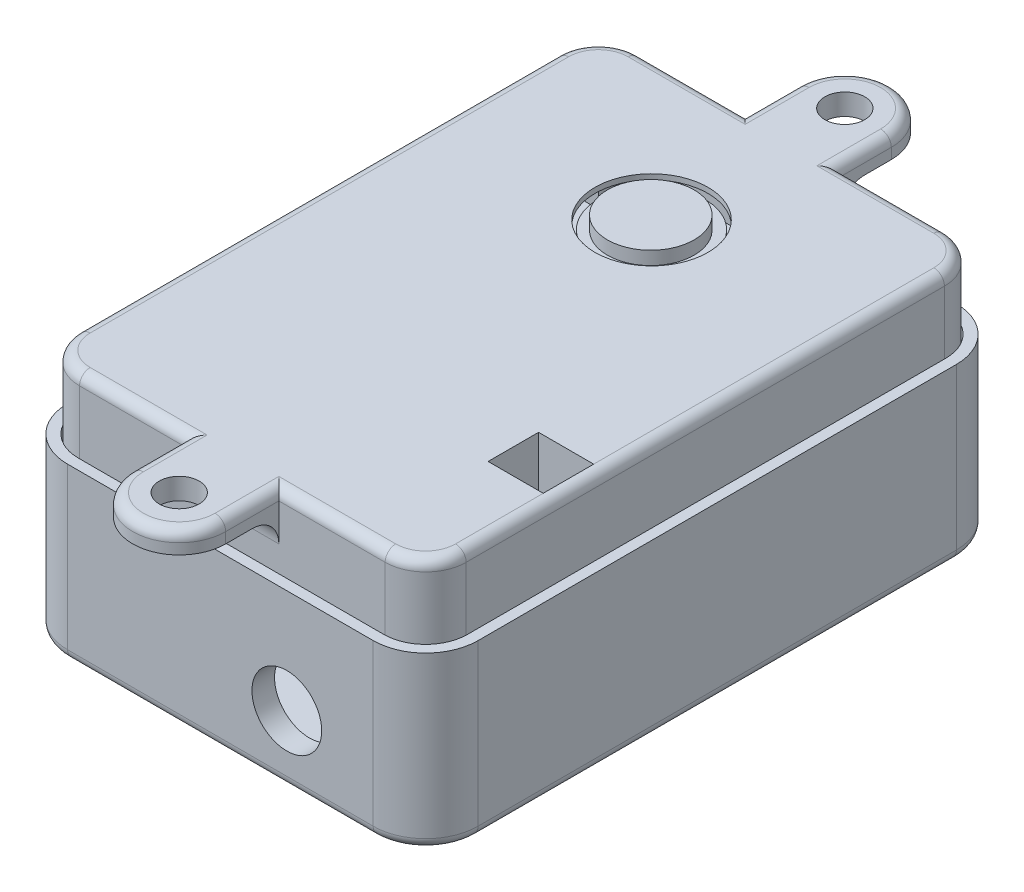
SolidWorks part; units mm, degrees
other "ESP32 Cam"
ref_plane "Front Plane" through (0, 0, 0) normal (0, 0, 1) x (1, 0, 0)
ref_plane "Top Plane" through (0, 0, 0) normal (0, 1, 0) x (1, 0, 0)
ref_plane "Right Plane" through (0, 0, 0) normal (1, 0, 0) x (0, 0, -1)
sketch "Sketch1" plane through (0, 0, 0) normal (0, 1, 0) x (1, 0, 0)
  line L1 (-11.5, 20) -> (11.5, 20)
  line L2 (-13.5, 18) -> (-13.5, -18)
  line L3 (-11.5, -20) -> (11.5, -20)
  line L4 (13.5, 18) -> (13.5, -18)
  line L5 (-13.5, 20) -> (13.5, -20) construction
  line L6 (-13.5, -20) -> (13.5, 20) construction
  arc A0 (-11.5, 20) -> (-13.5, 18) centre (-11.5, 18) ccw
  arc A1 (11.5, 20) -> (13.5, 18) centre (11.5, 18) cw
  arc A2 (11.5, -20) -> (13.5, -18) centre (11.5, -18) ccw
  arc A3 (-13.5, -18) -> (-11.5, -20) centre (-11.5, -18) ccw
  point P0 (0, 0)
  dimension "D3" = 2
  dimension "D1" = 27
  dimension "D2" = 40
extrude "Boss-Extrude1" add sketch "Sketch1" along normal blind 1
sketch "Sketch2" plane through (0, 1, 0) normal (0, 1, 0) x (1, 0, 0)
  line L0 (0, 0) -> (0, 20) construction
  line L1 (11.5, 20) -> (-11.5, 20) construction
  line L3 (-7.5, 20) -> (7.5, 20)
  line L4 (-7.5, 20) -> (-7.5, 5)
  line L5 (-7.5, 5) -> (7.5, 5)
  line L6 (7.5, 20) -> (7.5, 5)
  line L7 (-7.5, 20) -> (7.5, 5) construction
  line L8 (-7.5, 5) -> (7.5, 20) construction
  point P5 (0, 12.5)
  dimension "D1" = 15
extrude "Boss-Extrude2" add sketch "Sketch2" along normal blind 2
sketch "Sketch3" plane through (0, 3, 0) normal (0, 1, 0) x (1, 0, 0)
  line L0 (0, 5) -> (0, 20) construction
  line L1 (-7.5, 5) -> (7.5, 5) construction
  line L2 (7.5, 20) -> (-7.5, 20) construction
  circle A0 centre (0, 10.5) radius 4
  dimension "D1" = 8
  dimension "D2" = 5.5
extrude "Boss-Extrude3" add sketch "Sketch3" along normal blind 6.25
sketch "Sketch5" plane through (0, 1, 0) normal (0, 1, 0) x (1, 0, 0)
  line L0 (-11.5, -20) -> (11.5, -20) construction
  line L1 (10, -8) -> (13, -8)
  line L2 (10, -8) -> (10, -11)
  line L3 (10, -11) -> (13, -11)
  line L4 (13, -8) -> (13, -11)
  line L5 (10, -8) -> (13, -11) construction
  line L6 (10, -11) -> (13, -8) construction
  line L7 (13.5, -18) -> (13.5, 18) construction
  point P0 (11.5, -9.5)
  dimension "D1" = 3
  dimension "D2" = 10.5
  dimension "D3" = 2
extrude "Boss-Extrude4" add sketch "Sketch5" along normal blind 1
sketch "Sketch6" plane through (0, 9.25, 0) normal (0, 1, 0) x (1, 0, 0)
  line L37 (7.5, 21.05) -> (-7.5, 21.05)
  line L38 (-7.5, 21.05) -> (-11.5, 21.05)
  line L39 (-14.55, 18) -> (-14.55, -18)
  line L40 (-11.5, -21.05) -> (11.5, -21.05)
  line L41 (14.55, -18) -> (14.55, 18)
  line L42 (11.5, 21.05) -> (7.5, 21.05)
  line L43 (7.5, 20.25) -> (-7.5, 20.25)
  line L44 (11.5, 20.25) -> (7.5, 20.25)
  line L45 (13.75, -18) -> (13.75, 18)
  line L46 (-11.5, -20.25) -> (11.5, -20.25)
  line L47 (-13.75, 18) -> (-13.75, -18)
  line L48 (-7.5, 20.25) -> (-11.5, 20.25)
  line L55 (7.5, 20.25) -> (-7.5, 20.25) construction
  line L56 (11.5, 20.25) -> (7.5, 20.25) construction
  line L57 (13.75, -18) -> (13.75, 18) construction
  line L58 (-11.5, -20.25) -> (11.5, -20.25) construction
  line L59 (-13.75, 18) -> (-13.75, -18) construction
  line L60 (-7.5, 20.25) -> (-11.5, 20.25) construction
  circle A6 centre (0, 10.5) radius 4.25
  circle A8 centre (0, 10.5) radius 4.25
  arc A36 (-11.5, 21.05) -> (-14.55, 18) centre (-11.5, 18) ccw
  arc A37 (-14.55, -18) -> (-11.5, -21.05) centre (-11.5, -18) ccw
  arc A38 (11.5, -21.05) -> (14.55, -18) centre (11.5, -18) ccw
  arc A39 (14.55, 18) -> (11.5, 21.05) centre (11.5, 18) ccw
  arc A40 (13.75, 18) -> (11.5, 20.25) centre (11.5, 18) ccw
  arc A41 (11.5, -20.25) -> (13.75, -18) centre (11.5, -18) ccw
  arc A42 (-13.75, -18) -> (-11.5, -20.25) centre (-11.5, -18) ccw
  arc A43 (-11.5, 20.25) -> (-13.75, 18) centre (-11.5, 18) ccw
  arc A44 (13.75, 18) -> (11.5, 20.25) centre (11.5, 18) ccw construction
  arc A45 (11.5, -20.25) -> (13.75, -18) centre (11.5, -18) ccw construction
  arc A46 (-13.75, -18) -> (-11.5, -20.25) centre (-11.5, -18) ccw construction
  arc A47 (-11.5, 20.25) -> (-13.75, 18) centre (-11.5, 18) ccw construction
  dimension "D1" = 0.25
  dimension "D2" = 0.8
  dimension "D3" = 0.25
extrude "Boss-Extrude5" add sketch "Sketch6" along normal blind 0.4 from offset 0.25 separate body
sketch "Sketch8" plane through (0, 9.5, 0) normal (0, -1, 0) x (1, 0, 0)
  line L4 (-11.5, -21.05) -> (11.5, -21.05)
  line L5 (14.55, -18) -> (14.55, 18)
  line L6 (11.5, 21.05) -> (-11.5, 21.05)
  line L7 (-14.55, 18) -> (-14.55, -18)
  line L8 (-11.5, -21.05) -> (11.5, -21.05)
  line L9 (14.55, -18) -> (14.55, 18)
  line L10 (11.5, 21.05) -> (-11.5, 21.05)
  line L11 (-14.55, 18) -> (-14.55, -18)
  line L16 (-11.5, -20.25) -> (11.5, -20.25)
  line L17 (13.75, -18) -> (13.75, 18)
  line L18 (11.5, 20.25) -> (-11.5, 20.25)
  line L19 (-13.75, 18) -> (-13.75, -18)
  line L20 (-11.5, -20.25) -> (11.5, -20.25)
  line L21 (13.75, -18) -> (13.75, 18)
  line L22 (11.5, 20.25) -> (-11.5, 20.25)
  line L23 (-13.75, 18) -> (-13.75, -18)
  arc A4 (11.5, -21.05) -> (14.55, -18) centre (11.5, -18) ccw
  arc A5 (14.55, 18) -> (11.5, 21.05) centre (11.5, 18) ccw
  arc A6 (-11.5, 21.05) -> (-14.55, 18) centre (-11.5, 18) ccw
  arc A7 (-14.55, -18) -> (-11.5, -21.05) centre (-11.5, -18) ccw
  arc A8 (11.5, -21.05) -> (14.55, -18) centre (11.5, -18) ccw
  arc A9 (14.55, 18) -> (11.5, 21.05) centre (11.5, 18) ccw
  arc A10 (-11.5, 21.05) -> (-14.55, 18) centre (-11.5, 18) ccw
  arc A11 (-14.55, -18) -> (-11.5, -21.05) centre (-11.5, -18) ccw
  arc A16 (11.5, -20.25) -> (13.75, -18) centre (11.5, -18) ccw
  arc A17 (13.75, 18) -> (11.5, 20.25) centre (11.5, 18) ccw
  arc A18 (-11.5, 20.25) -> (-13.75, 18) centre (-11.5, 18) ccw
  arc A19 (-13.75, -18) -> (-11.5, -20.25) centre (-11.5, -18) ccw
  arc A20 (11.5, -20.25) -> (13.75, -18) centre (11.5, -18) ccw
  arc A21 (13.75, 18) -> (11.5, 20.25) centre (11.5, 18) ccw
  arc A22 (-11.5, 20.25) -> (-13.75, 18) centre (-11.5, 18) ccw
  arc A23 (-13.75, -18) -> (-11.5, -20.25) centre (-11.5, -18) ccw
  dimension "D1" = 0
  dimension "D2" = 0.8
extrude "Boss-Extrude7" add sketch "Sketch8" along normal up to vertex (9.5 mm away) up to point (-11.5, 0, 20)
sketch "Sketch9" plane through (0, 9.5, 0) normal (0, -1, 0) x (1, 0, 0)
  line L0 (13.75, 18) -> (11.5, 18)
  line L1 (11.5, 18) -> (11.5, 20.25)
  line L2 (6.0225, 0) -> (-6.0225, 0) construction
  line L3 (11.5, -18) -> (11.5, -20.25)
  line L4 (13.75, -18) -> (11.5, -18)
  line L5 (0, -6.0225) -> (0, 6.0225) construction
  line L6 (-13.75, -18) -> (-11.5, -18)
  line L7 (-11.5, -18) -> (-11.5, -20.25)
  line L8 (-11.5, 18) -> (-11.5, 20.25)
  line L9 (-13.75, 18) -> (-11.5, 18)
  arc A0 (13.75, 18) -> (11.5, 20.25) centre (11.5, 18) ccw construction
  arc A1 (13.75, 18) -> (11.5, 20.25) centre (11.5, 18) ccw
  arc A2 (13.75, -18) -> (11.5, -20.25) centre (11.5, -18) cw
  arc A3 (-13.75, -18) -> (-11.5, -20.25) centre (-11.5, -18) ccw
  arc A4 (-13.75, 18) -> (-11.5, 20.25) centre (-11.5, 18) cw
extrude "Boss-Extrude9" add sketch "Sketch9" along normal offset from surface (8.4 mm away) 0.1 up to face at (0, 1, -4.1667)
sketch "Sketch11" plane through (0, 9.9, 0) normal (0, 1, 0) x (1, 0, 0)
  line L1 (13.75, -7.6) -> (9.6, -7.6)
  line L2 (9.6, -7.6) -> (9.6, -11.4)
  line L3 (9.6, -11.4) -> (13.75, -11.4)
  line L4 (13, -11) -> (13, -8)
  line L5 (13, -8) -> (10, -8)
  line L6 (10, -8) -> (10, -11)
  line L7 (10, -11) -> (13, -11)
  line L8 (13, -11) -> (13, -8) construction
  line L9 (13, -8) -> (10, -8) construction
  line L10 (10, -8) -> (10, -11) construction
  line L11 (10, -11) -> (13, -11) construction
  line L12 (13.75, 18) -> (13.75, -18) construction
  line L13 (13.75, -7.6) -> (13.75, -11.4)
  line L14 (9.6, -11.4) -> (13.4, -11.4) construction
  line L15 (13.4, -11.4) -> (13.4, -7.6) construction
  line L16 (13.4, -7.6) -> (9.6, -7.6) construction
  dimension "D1" = 0
  dimension "D2" = 0.4
extrude "Cut-Extrude1" cut sketch "Sketch11" against normal up to vertex (0.4 mm away) up to point (11.5, 9.5, 18)
sketch "Sketch12" plane through (0, 0, 0) normal (0, -1, 0) x (1, 0, 0)
  line L0 (0, 0) -> (0, 20) construction
  line L1 (-11.5, 20) -> (11.5, 20) construction
  line L3 (9.375, -5.65) -> (-9.375, -5.65)
  line L4 (9.375, -5.65) -> (9.375, 20)
  line L5 (9.375, 20) -> (-9.375, 20)
  line L6 (-9.375, -5.65) -> (-9.375, 20)
  line L7 (9.375, -5.65) -> (-9.375, 20) construction
  line L8 (9.375, 20) -> (-9.375, -5.65) construction
  point P5 (0, 7.175)
  dimension "D1" = 18.75
  dimension "D2" = 25.65
extrude "Boss-Extrude10" add sketch "Sketch12" along normal blind 0.75
sketch "Sketch13" plane through (0, -0.75, 0) normal (0, -1, 0) x (1, 0, 0)
  line L0 (0, -5.65) -> (0, 20) construction
  line L1 (-9.375, -5.65) -> (9.375, -5.65) construction
  line L2 (8, 12.35) -> (2, 12.35) construction
  line L3 (2, 12.35) -> (-8, 12.35)
  line L4 (8, 9.35) -> (8, -5.15)
  line L5 (8, -5.15) -> (-8, -5.15)
  line L6 (-8, 12.35) -> (-8, -5.15)
  line L7 (8, 12.35) -> (-8, -5.15) construction
  line L8 (8, -5.15) -> (-8, 12.35) construction
  line L11 (8, 9.35) -> (2, 9.35)
  line L12 (2, 12.35) -> (2, 9.35)
  line L13 (8, 12.35) -> (8, 9.35) construction
  line L14 (9.375, 20) -> (11.5, 20) construction
  point P5 (0, 3.6)
  dimension "D1" = 16
  dimension "D2" = 17.5
  dimension "D3" = 3
  dimension "D4" = 6
  dimension "D5" = 0.5
extrude "Boss-Extrude11" add sketch "Sketch13" along normal blind 2.3
sketch "Sketch14" plane through (0, 0, 0) normal (0, -1, 0) x (1, 0, 0)
  line L0 (9.375, 20) -> (11.5, 20) construction
  line L1 (12.75, -16.2) -> (10.25, -16.2)
  line L2 (12.75, -16.2) -> (12.75, 4)
  line L3 (12.75, 4) -> (10.25, 4)
  line L4 (10.25, -16.2) -> (10.25, 4)
  line L5 (12.75, -16.2) -> (10.25, 4) construction
  line L6 (12.75, 4) -> (10.25, -16.2) construction
  line L7 (13.5, 18) -> (13.5, -18) construction
  point P0 (11.5, -6.1)
  dimension "D1" = 20.2
  dimension "D2" = 2.5
  dimension "D3" = 16
  dimension "D4" = 0.75
extrude "Boss-Extrude12" add sketch "Sketch14" along normal blind 2.45
sketch "Sketch16" plane through (0, -2.45, 0) normal (0, -1, 0) x (1, 0, 0)
  line L0 (11.5, 4) -> (11.5, -16.2) construction
  line L3 (11.2, 3) -> (11.8, 3)
  line L8 (11.2, 3) -> (11.2, 2.4)
  line L9 (11.2, 2.4) -> (11.8, 2.4)
  line L10 (11.8, 3) -> (11.8, 2.4)
  line L11 (12.75, 4) -> (10.25, 4) construction
  line L12 (10.25, -16.2) -> (12.75, -16.2) construction
  dimension "D1" = 0.6
  dimension "D2" = 1
extrude "Boss-Extrude14" add sketch "Sketch16" along normal blind 5.5
pattern_linear "LPattern1" count 8 spacing 2.5 along (0, 0, -1) of "Boss-Extrude14"
sketch "Sketch17" plane through (0, -3.05, 0) normal (0, -1, 0) x (1, 0, 0)
  line L14 (-11.5, -21.95) -> (11.5, -21.95)
  line L15 (15.45, -18) -> (15.45, 18)
  line L16 (-11.5, -21.15) -> (11.5, -21.15)
  line L17 (-14.65, 18) -> (-14.65, -18)
  line L18 (11.5, 21.15) -> (-11.5, 21.15)
  line L19 (-11.5, -21.15) -> (11.5, -21.15)
  line L20 (-14.65, 18) -> (-14.65, -18)
  line L21 (11.5, 21.15) -> (-11.5, 21.15)
  line L22 (14.65, -18) -> (14.65, 18)
  line L23 (11.5, 21.95) -> (-11.5, 21.95)
  line L24 (-15.45, 18) -> (-15.45, -18)
  arc A16 (11.5, -21.95) -> (15.45, -18) centre (11.5, -18) ccw
  arc A17 (15.45, 18) -> (11.5, 21.95) centre (11.5, 18) ccw
  arc A18 (-11.5, 21.95) -> (-15.45, 18) centre (-11.5, 18) ccw
  arc A19 (-15.45, -18) -> (-11.5, -21.95) centre (-11.5, -18) ccw
  arc A20 (11.5, -21.15) -> (14.65, -18) centre (11.5, -18) ccw
  arc A21 (-14.65, -18) -> (-11.5, -21.15) centre (-11.5, -18) ccw
  arc A22 (-11.5, 21.15) -> (-14.65, 18) centre (-11.5, 18) ccw
  arc A23 (14.65, 18) -> (11.5, 21.15) centre (11.5, 18) ccw
  arc A24 (11.5, -21.15) -> (14.65, -18) centre (11.5, -18) ccw
  arc A25 (-14.65, -18) -> (-11.5, -21.15) centre (-11.5, -18) ccw
  arc A26 (-11.5, 21.15) -> (-14.65, 18) centre (-11.5, 18) ccw
  arc A27 (14.65, 18) -> (11.5, 21.15) centre (11.5, 18) ccw
  dimension "D1" = 0.1
  dimension "D2" = 0.8
extrude "Boss-Extrude15" add sketch "Sketch17" against normal blind 12.5 from offset 5 separate body
sketch "Sketch18" plane through (0, -8.05, 0) normal (0, -1, 0) x (1, 0, 0)
  line L0 (-11.5, -20.25) -> (11.5, -20.25) construction
  line L1 (-13.75, 18) -> (-13.75, -18) construction
  line L2 (13.75, -18) -> (13.75, 18) construction
  line L3 (11.5, 20.25) -> (-11.5, 20.25) construction
  line L4 (-11.5, -20.25) -> (11.5, -20.25)
  line L5 (-13.75, 18) -> (-13.75, -18)
  line L6 (13.75, -18) -> (13.75, 18)
  line L7 (11.5, 20.25) -> (-11.5, 20.25)
  line L8 (-11.5, -21.15) -> (11.5, -21.15) construction
  line L9 (-14.65, 18) -> (-14.65, -18) construction
  line L10 (11.5, 21.15) -> (-11.5, 21.15) construction
  line L11 (14.65, -18) -> (14.65, 18) construction
  line L12 (-11.5, -21.15) -> (11.5, -21.15)
  line L13 (-14.65, 18) -> (-14.65, -18)
  line L14 (11.5, 21.15) -> (-11.5, 21.15)
  line L15 (14.65, -18) -> (14.65, 18)
  arc A0 (11.5, -20.25) -> (13.75, -18) centre (11.5, -18) ccw construction
  arc A1 (-13.75, -18) -> (-11.5, -20.25) centre (-11.5, -18) ccw construction
  arc A2 (-11.5, 20.25) -> (-13.75, 18) centre (-11.5, 18) ccw construction
  arc A3 (13.75, 18) -> (11.5, 20.25) centre (11.5, 18) ccw construction
  arc A4 (11.5, -20.25) -> (13.75, -18) centre (11.5, -18) ccw
  arc A5 (-13.75, -18) -> (-11.5, -20.25) centre (-11.5, -18) ccw
  arc A6 (-11.5, 20.25) -> (-13.75, 18) centre (-11.5, 18) ccw
  arc A7 (13.75, 18) -> (11.5, 20.25) centre (11.5, 18) ccw
  arc A8 (11.5, -21.15) -> (14.65, -18) centre (11.5, -18) ccw construction
  arc A9 (-14.65, -18) -> (-11.5, -21.15) centre (-11.5, -18) ccw construction
  arc A10 (-11.5, 21.15) -> (-14.65, 18) centre (-11.5, 18) ccw construction
  arc A11 (14.65, 18) -> (11.5, 21.15) centre (11.5, 18) ccw construction
  arc A12 (11.5, -21.15) -> (14.65, -18) centre (11.5, -18) ccw
  arc A13 (-14.65, -18) -> (-11.5, -21.15) centre (-11.5, -18) ccw
  arc A14 (-11.5, 21.15) -> (-14.65, 18) centre (-11.5, 18) ccw
  arc A15 (14.65, 18) -> (11.5, 21.15) centre (11.5, 18) ccw
extrude "Boss-Extrude16" add sketch "Sketch18" against normal offset from surface (7.95 mm away) 0.1 up to face at (0, 0, 0)
sketch "Sketch19" plane through (0, -8.05, 0) normal (0, -1, 0) x (1, 0, 0)
  line L165 (0, -6.0225) -> (0, 6.0225) construction
  line L166 (-13.25, -16.7) -> (-13.25, 4.5)
  line L167 (-13.25, 4.5) -> (-9.75, 4.5)
  line L168 (-9.75, 4.5) -> (-9.75, -16.7)
  line L169 (13.25, 4.5) -> (9.75, 4.5)
  line L170 (13.25, -16.7) -> (13.25, 4.5)
  line L171 (9.75, -16.7) -> (13.25, -16.7)
  line L172 (9.75, 4.5) -> (9.75, -16.7)
  line L173 (13.25, 4.5) -> (9.75, 4.5)
  line L174 (13.25, -16.7) -> (13.25, 4.5)
  line L175 (9.75, -16.7) -> (13.25, -16.7)
  line L176 (9.75, 4.5) -> (9.75, -16.7)
  line L177 (-9.75, -16.7) -> (-13.25, -16.7)
  line L178 (11.5, 21.95) -> (-11.5, 21.95) construction
  line L179 (-15.45, 18) -> (-15.45, -18) construction
  line L180 (-11.5, -21.95) -> (11.5, -21.95) construction
  line L181 (15.45, -18) -> (15.45, 18) construction
  line L182 (11.5, 21.95) -> (-11.5, 21.95)
  line L183 (-15.45, 18) -> (-15.45, -18)
  line L184 (-11.5, -21.95) -> (11.5, -21.95)
  line L185 (15.45, -18) -> (15.45, 18)
  arc A0 (15.45, 18) -> (11.5, 21.95) centre (11.5, 18) ccw construction
  arc A1 (-11.5, 21.95) -> (-15.45, 18) centre (-11.5, 18) ccw construction
  arc A2 (-15.45, -18) -> (-11.5, -21.95) centre (-11.5, -18) ccw construction
  arc A3 (11.5, -21.95) -> (15.45, -18) centre (11.5, -18) ccw construction
  arc A4 (15.45, 18) -> (11.5, 21.95) centre (11.5, 18) ccw
  arc A5 (-11.5, 21.95) -> (-15.45, 18) centre (-11.5, 18) ccw
  arc A6 (-15.45, -18) -> (-11.5, -21.95) centre (-11.5, -18) ccw
  arc A7 (11.5, -21.95) -> (15.45, -18) centre (11.5, -18) ccw
  dimension "D1" = 0.5
extrude "Boss-Extrude17" add sketch "Sketch19" along normal blind 0.4
sketch "Sketch20" plane through (0, 0, 21.95) normal (0, 0, 1) x (1, 0, 0)
  line L0 (2, -3.05) -> (2, -0.75) construction
  line L1 (8, -0.75) -> (2, -0.75) construction
  line L2 (8, -3.05) -> (8, -0.75) construction
  line L3 (8, -3.05) -> (2, -3.05) construction
  line L4 (2, -3.05) -> (2, -0.75) construction
  line L5 (8, -0.75) -> (2, -0.75) construction
  line L6 (8, -3.05) -> (8, -0.75) construction
  line L7 (8, -3.05) -> (2, -3.05) construction
  line L8 (8, -3.05) -> (2, -0.75) construction
  line L9 (8, -0.75) -> (2, -3.05) construction
  line L10 (5, -1.9) -> (5, -3.375) construction
  line L12 (9.375, -0.75) -> (-9.375, -0.75) construction
  line L13 (9.375, -0.75) -> (-9.375, -0.75) construction
  circle A0 centre (5, -3.375) radius 2.625
  dimension "D1" = 5.25
extrude "Cut-Extrude2" cut sketch "Sketch20" against normal up to next (1.7 mm away) contours A0 region at (5, -3.375, 21.95)
sketch "Sketch22" plane through (0, -8.05, 0) normal (0, 1, 0) x (1, 0, 0)
  line L0 (13.75, -18) -> (11.5, -18)
  line L1 (11.5, -18) -> (11.5, -20.25)
  line L2 (-6.0225, 0) -> (6.0225, 0) construction
  line L3 (11.5, 18) -> (11.5, 20.25)
  line L4 (13.75, 18) -> (11.5, 18)
  line L5 (0, -6.0225) -> (0, 6.0225) construction
  line L6 (-13.75, 18) -> (-11.5, 18)
  line L7 (-11.5, 18) -> (-11.5, 20.25)
  line L8 (-11.5, -18) -> (-11.5, -20.25)
  line L9 (-13.75, -18) -> (-11.5, -18)
  arc A0 (11.5, -20.25) -> (13.75, -18) centre (11.5, -18) ccw construction
  arc A1 (11.5, -20.25) -> (13.75, -18) centre (11.5, -18) ccw
  arc A2 (11.5, 20.25) -> (13.75, 18) centre (11.5, 18) cw
  arc A3 (-11.5, 20.25) -> (-13.75, 18) centre (-11.5, 18) ccw
  arc A4 (-11.5, -20.25) -> (-13.75, -18) centre (-11.5, -18) cw
extrude "Boss-Extrude18" add sketch "Sketch22" along normal up to vertex (7.95 mm away) up to point (11.5, -0.1, -20.25)
sketch "Sketch23" plane through (0, 9.5, 0) normal (0, -1, 0) x (1, 0, 0)
  line L1 (9.6, 11.4) -> (13.75, 11.4) construction
  line L2 (9.6, 7.6) -> (9.6, 11.4) construction
  line L3 (13.75, 7.6) -> (9.6, 7.6) construction
  line L5 (9.6, 11.4) -> (13.75, 11.4)
  line L6 (9.6, 7.6) -> (9.6, 11.4)
  line L7 (13.75, 7.6) -> (9.6, 7.6)
  line L8 (13.75, 6.8) -> (8.8, 6.8)
  line L9 (8.8, 6.8) -> (8.8, 12.2)
  line L10 (8.8, 12.2) -> (13.75, 12.2)
  line L11 (13.75, 7.6) -> (13.75, 6.8)
  line L12 (13.75, 12.2) -> (13.75, 11.4)
  dimension "D1" = 0.8
extrude "Boss-Extrude19" add sketch "Sketch23" along normal offset from surface (7.4 mm away) 1 up to face at (12.4053, 1.1, 18.9053)
mirror "Mirror1" about plane through (0, 0, 0) normal (1, 0, 0) of "LPattern1", "Boss-Extrude12"
sketch "Sketch24" plane through (0, 9.9, 0) normal (0, 1, 0) x (1, 0, 0)
  line L0 (0, 0) -> (0, 25.05) construction
  line L2 (-3.5, 25.05) -> (-3.5, 21.05)
  line L8 (11.5, 21.05) -> (-11.5, 21.05) construction
  line L9 (3.5, 25.05) -> (3.5, 21.05)
  line L10 (-3.5, 21.05) -> (3.5, 21.05)
  line L11 (-6.0225, 0) -> (6.0225, 0) construction
  line L12 (-3.5, -21.05) -> (3.5, -21.05)
  line L13 (3.5, -25.05) -> (3.5, -21.05)
  line L14 (-3.5, -25.05) -> (-3.5, -21.05)
  circle A1 centre (0, 25.05) radius 1.5
  arc A2 (3.5, 25.05) -> (-3.5, 25.05) centre (0, 25.05) ccw
  circle A3 centre (0, 25.05) radius 3.5 construction
  arc A4 (3.5, -25.05) -> (-3.5, -25.05) centre (0, -25.05) cw
  circle A5 centre (0, -25.05) radius 1.5
  dimension "D2" = 3
  dimension "D1" = 2
extrude "Boss-Extrude20" add sketch "Sketch24" against normal blind 1.6
fillet "Fillet1" radius 2 2 edges at (0, 8.3, 21.05) (0, 8.3, -21.05)
fillet "Fillet2" radius 0.8 8 edges at (-14.2931, -8.45, -20.7931) (-15.45, -8.45, 0) (-14.2931, -8.45, 20.7931) (0, -8.45, 21.95) (14.2931, -8.45, 20.7931) (15.45, -8.45, 0) (14.2931, -8.45, -20.7931) (0, -8.45, -21.95)
fillet "Fillet3" radius 0.8 16 edges at (3.5, 9.9, 23.05) (0, 9.9, 28.55) (3.5, 9.9, -23.05) (0, 9.9, -28.55) (-7.5, 9.9, 21.05) (-13.6567, 9.9, 20.1567) (-14.55, 9.9, 0) (-13.6567, 9.9, -20.1567) (-3.5, 9.9, 23.05) (-3.5, 9.9, -23.05) (-7.5, 9.9, -21.05) (7.5, 9.9, 21.05) (13.6567, 9.9, 20.1567) (7.5, 9.9, -21.05) (13.6567, 9.9, -20.1567) (14.55, 9.9, 0)
sketch "Sketch25" plane through (0, 9.25, 0) normal (0, 1, 0) x (1, 0, 0)
  circle A0 centre (0, 10.4454) radius 3.2626
extrude "Boss-Extrude21" add sketch "Sketch25" along normal blind 1
